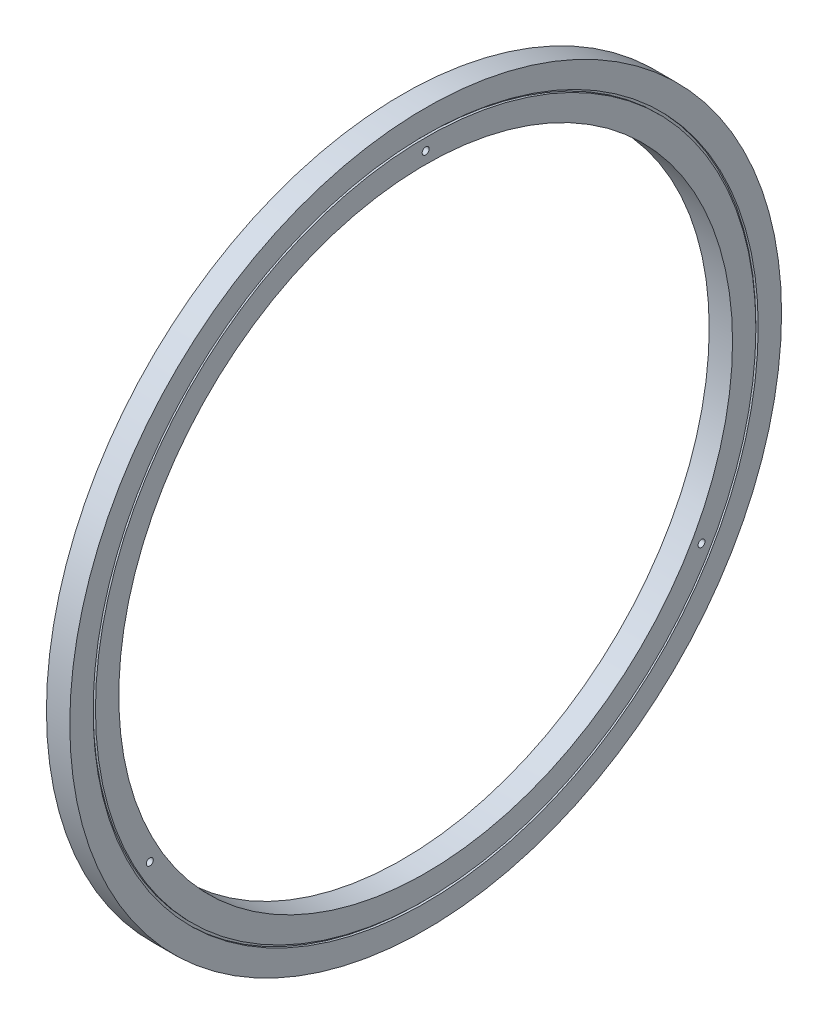
SolidWorks part; units mm, degrees
ref_plane "Front Plane" through (0, 0, 0) normal (0, 0, 1) x (1, 0, 0)
ref_plane "Top Plane" through (0, 0, 0) normal (0, 1, 0) x (1, 0, 0)
ref_plane "Right Plane" through (0, 0, 0) normal (1, 0, 0) x (0, 0, -1)
sketch "Sketch1" plane through (0, 0, 0) normal (1, 0, 0) x (0, 0, -1)
  circle A0 centre (0, 0) radius 152.5
  circle A1 centre (0, 0) radius 142.5
  circle A2 centre (0, 0) radius 141.5
  circle A3 centre (0, 0) radius 131.5
  dimension "D1" = 10
  dimension "D2" = 1
  dimension "D3" = 10
extrude "Boss-Extrude2" add sketch "Sketch1" along normal mid plane 10 contours A2 A3 | A0 A1 region at (0, 0, 148.1866) region at (0, 0, 137.4978)
extrude "Boss-Extrude3" add sketch "Sketch1<4>" along normal mid plane 8 contours A1 A2 region at (0, 0, 142.0969)
sketch "Sketch1<4>" plane through (0, 0, 0) normal (1, 0, 0) x (0, 0, -1) same geometry as "Sketch1"
sketch "Sketch2" plane through (5, 0, 0) normal (1, 0, 0) x (0, 0, -1)
  line L0 (0, 0) -> (0, 131.5)
  circle A0 centre (0, 0) radius 131.5 construction
  circle A3 centre (0, 136.5) radius 1.5
  circle A4 centre (118.2125, -68.25) radius 1.5
  circle A5 centre (-118.2125, -68.25) radius 1.5
  point P16 (0, 0)
  dimension "D1" = 3
extrude "Cut-Extrude1" cut sketch "Sketch2" against normal blind 4 contours A3 | A4 | A5 region at (5, 136.5, 0) region at (5, -68.25, -118.2125) region at (5, -68.25, 118.2125)
